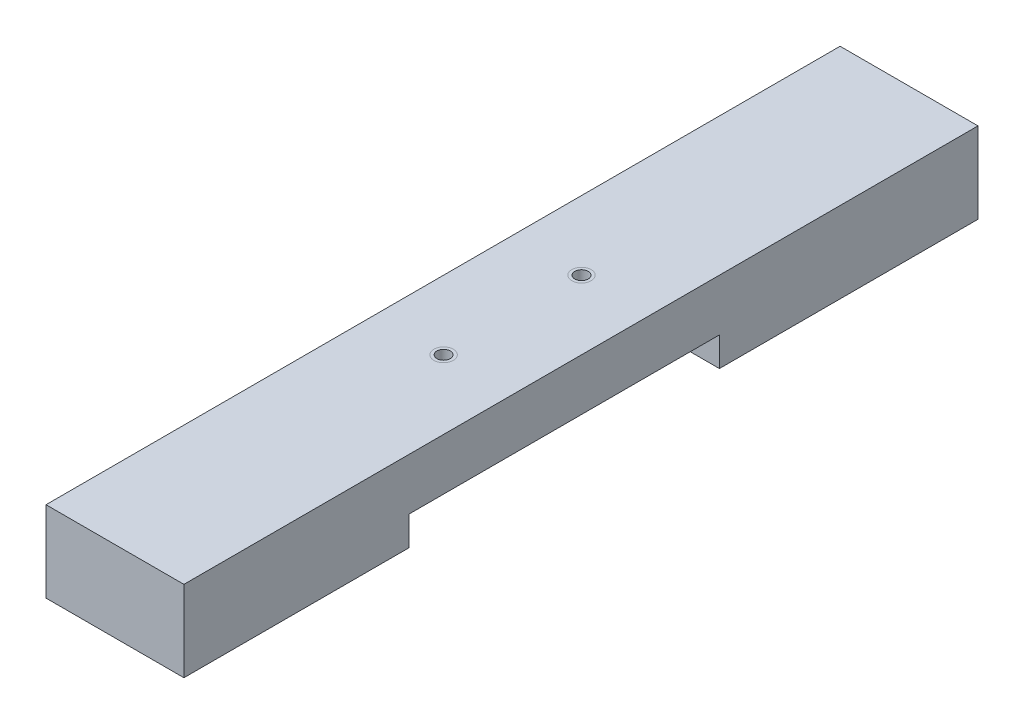
SolidWorks part; units mm, degrees
material "McMaster 6061-T6"
ref_plane "Front" through (0, 0, 0) normal (0, 0, 1) x (1, 0, 0)
ref_plane "Top" through (0, 0, 0) normal (0, 1, 0) x (1, 0, 0)
ref_plane "Right" through (0, 0, 0) normal (1, 0, 0) x (0, 0, -1)
sketch "Sketch1" plane through (0, 0, 0) normal (0, 0, 1) x (1, 0, 0)
  line L1 (0, 0) -> (101.6, 0)
  line L2 (0, 0) -> (0, 59.6)
  line L3 (0, 59.6) -> (101.6, 59.6)
  line L4 (101.6, 0) -> (101.6, 59.6)
  dimension "D1" = 59.6
  dimension "D2" = 101.6
extrude "Boss-Extrude1" add sketch "Sketch1" along normal blind 585.0001
sketch "Sketch2" plane through (0, 0, 0) normal (-1, 0, 0) x (0, 0, 1)
  line L0 (190.5, 0) -> (190.5, 21.5)
  line L1 (585.0001, 0) -> (0, 0) construction
  line L2 (190.5, 21.5) -> (419.1, 21.5)
  line L3 (419.1, 21.5) -> (419.1, 0)
  line L4 (419.1, 0) -> (190.5, 0)
  line L5 (0, 59.6) -> (0, 0) construction
  dimension "D1" = 190.5
  dimension "D2" = 21.5
  dimension "D3" = 228.6
extrude "Cut-Extrude1" cut sketch "Sketch2" against normal through all
sketch "Sketch5" plane through (0, 0, 0) normal (-1, 0, 0) x (0, 0, 1)
  arc A0 (6.7, 6.6) -> (13.3, 6.6) centre (10, 6.6) ccw construction
  arc A1 (13.3, 6.6) -> (6.7, 6.6) centre (10, 6.6) ccw construction
  arc A2 (6.7, 52.6) -> (13.3, 52.6) centre (10, 52.6) ccw construction
  arc A3 (13.3, 52.6) -> (6.7, 52.6) centre (10, 52.6) ccw construction
  arc A4 (6.7, 6.6) -> (13.3, 6.6) centre (10, 6.6) ccw
  arc A5 (13.3, 6.6) -> (6.7, 6.6) centre (10, 6.6) ccw
  arc A6 (6.7, 52.6) -> (13.3, 52.6) centre (10, 52.6) ccw
  arc A7 (13.3, 52.6) -> (6.7, 52.6) centre (10, 52.6) ccw
  arc A8 (170, 31.35) -> (170, 27.85) centre (170, 29.6) ccw construction
  arc A9 (170, 27.85) -> (170, 31.35) centre (170, 29.6) ccw construction
  arc A10 (110, 27.85) -> (110, 31.35) centre (110, 29.6) ccw construction
  arc A11 (110, 31.35) -> (110, 27.85) centre (110, 29.6) ccw construction
  arc A12 (50, 27.85) -> (50, 31.35) centre (50, 29.6) ccw construction
  arc A13 (50, 31.35) -> (50, 27.85) centre (50, 29.6) ccw construction
  arc A14 (170, 31.35) -> (170, 27.85) centre (170, 29.6) ccw
  arc A15 (170, 27.85) -> (170, 31.35) centre (170, 29.6) ccw
  arc A16 (110, 27.85) -> (110, 31.35) centre (110, 29.6) ccw
  arc A17 (110, 31.35) -> (110, 27.85) centre (110, 29.6) ccw
  arc A18 (50, 27.85) -> (50, 31.35) centre (50, 29.6) ccw
  arc A19 (50, 31.35) -> (50, 27.85) centre (50, 29.6) ccw
  arc A20 (530, 27.85) -> (530, 31.35) centre (530, 29.6) ccw construction
  arc A21 (530, 31.35) -> (530, 27.85) centre (530, 29.6) ccw construction
  arc A22 (470, 27.85) -> (470, 31.35) centre (470, 29.6) ccw construction
  arc A23 (470, 31.35) -> (470, 27.85) centre (470, 29.6) ccw construction
  arc A24 (410, 27.85) -> (410, 31.35) centre (410, 29.6) ccw construction
  arc A25 (410, 31.35) -> (410, 27.85) centre (410, 29.6) ccw construction
  arc A26 (350, 27.85) -> (350, 31.35) centre (350, 29.6) ccw construction
  arc A27 (350, 31.35) -> (350, 27.85) centre (350, 29.6) ccw construction
  arc A28 (290, 27.85) -> (290, 31.35) centre (290, 29.6) ccw construction
  arc A29 (290, 31.35) -> (290, 27.85) centre (290, 29.6) ccw construction
  arc A30 (230, 27.85) -> (230, 31.35) centre (230, 29.6) ccw construction
  arc A31 (230, 31.35) -> (230, 27.85) centre (230, 29.6) ccw construction
  arc A32 (530, 27.85) -> (530, 31.35) centre (530, 29.6) ccw
  arc A33 (530, 31.35) -> (530, 27.85) centre (530, 29.6) ccw
  arc A34 (470, 27.85) -> (470, 31.35) centre (470, 29.6) ccw
  arc A35 (470, 31.35) -> (470, 27.85) centre (470, 29.6) ccw
  arc A36 (410, 27.85) -> (410, 31.35) centre (410, 29.6) ccw
  arc A37 (410, 31.35) -> (410, 27.85) centre (410, 29.6) ccw
  arc A38 (350, 27.85) -> (350, 31.35) centre (350, 29.6) ccw
  arc A39 (350, 31.35) -> (350, 27.85) centre (350, 29.6) ccw
  arc A40 (290, 27.85) -> (290, 31.35) centre (290, 29.6) ccw
  arc A41 (290, 31.35) -> (290, 27.85) centre (290, 29.6) ccw
  arc A42 (230, 27.85) -> (230, 31.35) centre (230, 29.6) ccw
  arc A43 (230, 31.35) -> (230, 27.85) centre (230, 29.6) ccw
  arc A44 (582.3, 6.6) -> (575.7, 6.6) centre (579, 6.6) ccw construction
  arc A45 (575.7, 6.6) -> (582.3, 6.6) centre (579, 6.6) ccw construction
  arc A46 (562.7, 6.6) -> (569.3, 6.6) centre (566, 6.6) ccw construction
  arc A47 (569.3, 6.6) -> (562.7, 6.6) centre (566, 6.6) ccw construction
  arc A48 (575.7, 52.6) -> (582.3, 52.6) centre (579, 52.6) ccw construction
  arc A49 (582.3, 52.6) -> (575.7, 52.6) centre (579, 52.6) ccw construction
  arc A50 (562.7, 52.6) -> (569.3, 52.6) centre (566, 52.6) ccw construction
  arc A51 (569.3, 52.6) -> (562.7, 52.6) centre (566, 52.6) ccw construction
  arc A52 (582.3, 6.6) -> (575.7, 6.6) centre (579, 6.6) ccw
  arc A53 (575.7, 6.6) -> (582.3, 6.6) centre (579, 6.6) ccw
  arc A54 (562.7, 6.6) -> (569.3, 6.6) centre (566, 6.6) ccw
  arc A55 (569.3, 6.6) -> (562.7, 6.6) centre (566, 6.6) ccw
  arc A56 (575.7, 52.6) -> (582.3, 52.6) centre (579, 52.6) ccw
  arc A57 (582.3, 52.6) -> (575.7, 52.6) centre (579, 52.6) ccw
  arc A58 (562.7, 52.6) -> (569.3, 52.6) centre (566, 52.6) ccw
  arc A59 (569.3, 52.6) -> (562.7, 52.6) centre (566, 52.6) ccw
extrude "Cut-Extrude4" cut sketch "Sketch5" against normal blind 6.35 from surface contours A32 A33 | A34 A35 | A36 A37 | A38 A39 | A40 A41 | A42 A43 | A15 A14 | A16 A17 | A18 A19 starting at face at (0, 20.275, 298.65)
extrude "Cut-Extrude5" cut sketch "Sketch5<3>" against normal blind 25.4 from surface contours A54 A55 | A52 A53 | A56 A57 | A58 A59 | A4 A5 | A6 A7 region at (0, 6.6, 10) region at (0, 52.6, 10) region at (0, 6.6, 579) region at (0, 6.6, 566) region at (0, 52.6, 579) region at (0, 52.6, 566) starting at face at (0, 29.6, 528.25)
sketch "Sketch5<3>" plane through (0, 0, 0) normal (-1, 0, 0) x (0, 0, 1) same geometry as "Sketch5"
sketch "Sketch6" plane through (0, 21.5, 0) normal (0, -1, 0) x (1, 0, 0)
  circle A0 centre (50.8, 342.9) radius 4.9344 construction
  circle A1 centre (50.8, 241.3) radius 4.9344 construction
  circle A2 centre (50.8, 342.9) radius 4.9344
  circle A3 centre (50.8, 241.3) radius 4.9344
extrude "Cut-Extrude6" cut sketch "Sketch6" against normal through all
sketch "Sketch7" plane through (0, 59.6, 0) normal (0, 1, 0) x (1, 0, 0)
  circle A0 centre (50.8, -241.3) radius 7.1437
  circle A1 centre (50.8, -342.9) radius 7.1438
  dimension "D1" = 14.2875
split line "Split Line1"
